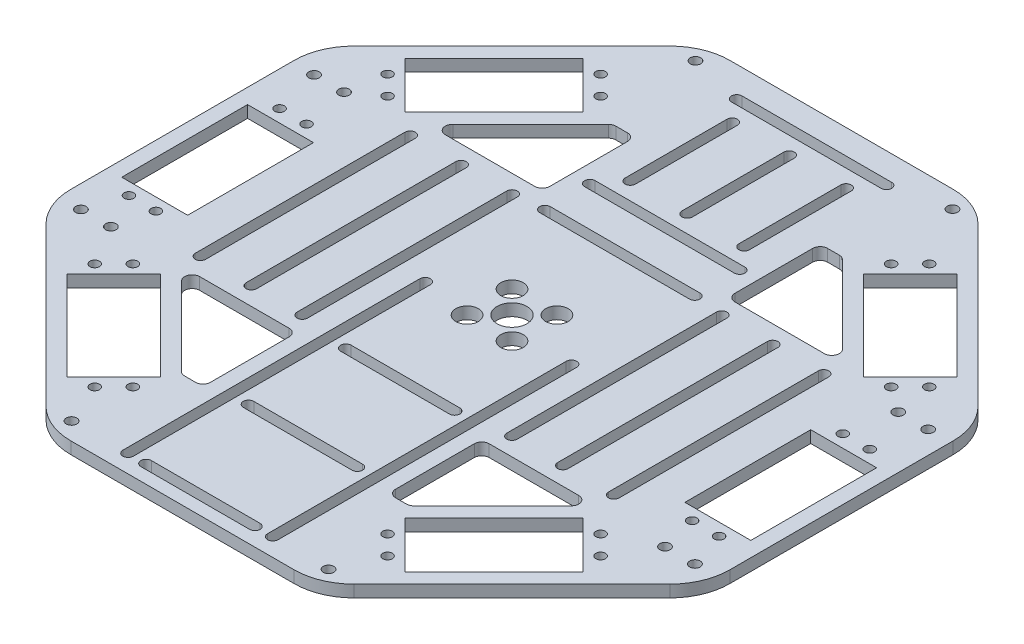
SolidWorks part; units mm, degrees
ref_plane "Front Plane" through (0, 0, 0) normal (0, 0, 1) x (1, 0, 0)
ref_plane "Top Plane" through (0, 0, 0) normal (0, 1, 0) x (1, 0, 0)
ref_plane "Right Plane" through (0, 0, 0) normal (1, 0, 0) x (0, 0, -1)
sketch "Sketch1" plane through (0, 0, 0) normal (0, 1, 0) x (1, 0, 0)
  line L1 (-110, -45.5635) -> (-45.5635, -110)
  line L2 (-45.5635, -110) -> (45.5635, -110)
  line L3 (45.5635, -110) -> (110, -45.5635)
  line L4 (110, -45.5635) -> (110, 45.5635)
  line L5 (110, 45.5635) -> (45.5635, 110)
  line L6 (45.5635, 110) -> (-45.5635, 110)
  line L7 (-45.5635, 110) -> (-110, 45.5635)
  line L8 (-110, 45.5635) -> (-110, -45.5635)
  line L12 (77.7817, -77.7817) -> (0, 0) construction
  line L21 (-20.4, -34.5422) -> (-34.5422, -20.4)
  line L22 (-20.4, -34.5422) -> (-50.0985, -64.2407)
  line L23 (-50.0985, -64.2407) -> (-64.2407, -50.0985)
  line L24 (-34.5422, -20.4) -> (-64.2407, -50.0985)
  line L25 (-38.85, -10) -> (-38.85, 10)
  line L26 (-38.85, -10) -> (-80.85, -10)
  line L27 (-80.85, -10) -> (-80.85, 10)
  line L28 (-38.85, 10) -> (-80.85, 10)
  line L29 (-34.5422, 20.4) -> (-20.4, 34.5422)
  line L30 (-34.5422, 20.4) -> (-64.2407, 50.0985)
  line L31 (-64.2407, 50.0985) -> (-50.0985, 64.2407)
  line L32 (-20.4, 34.5422) -> (-50.0985, 64.2407)
  line L37 (20.4, 34.5422) -> (34.5422, 20.4)
  line L38 (20.4, 34.5422) -> (50.0985, 64.2407)
  line L39 (50.0985, 64.2407) -> (64.2407, 50.0985)
  line L40 (34.5422, 20.4) -> (64.2407, 50.0985)
  line L41 (38.85, 10) -> (38.85, -10)
  line L42 (38.85, 10) -> (80.85, 10)
  line L43 (80.85, 10) -> (80.85, -10)
  line L44 (38.85, -10) -> (80.85, -10)
  circle A0 centre (0, 0) radius 110 construction
  circle A13 centre (0, 0) radius 110 construction
  circle A14 centre (-27.7186, -21.3546) radius 2.5
  circle A15 centre (-21.3546, -27.7186) radius 2.5
  circle A16 centre (-56.9221, -63.2861) radius 2.5
  circle A17 centre (-63.2861, -56.9221) radius 2.5
  circle A18 centre (0, 0) radius 110 construction
  circle A19 centre (-34.7, 4.5) radius 2.5
  circle A20 centre (-34.7, -4.5) radius 2.5
  circle A21 centre (-85, -4.5) radius 2.5
  circle A22 centre (-85, 4.5) radius 2.5
  circle A23 centre (0, 0) radius 110 construction
  circle A24 centre (-21.3546, 27.7186) radius 2.5
  circle A25 centre (-27.7186, 21.3546) radius 2.5
  circle A26 centre (-63.2861, 56.9221) radius 2.5
  circle A27 centre (-56.9221, 63.2861) radius 2.5
  circle A28 centre (0, 0) radius 110 construction
  circle A33 centre (0, 0) radius 110 construction
  circle A34 centre (27.7186, 21.3546) radius 2.5
  circle A35 centre (21.3546, 27.7186) radius 2.5
  circle A36 centre (56.9221, 63.2861) radius 2.5
  circle A37 centre (63.2861, 56.9221) radius 2.5
  circle A38 centre (0, 0) radius 110 construction
  circle A39 centre (34.7, -4.5) radius 2.5
  circle A40 centre (34.7, 4.5) radius 2.5
  circle A41 centre (85, 4.5) radius 2.5
  circle A42 centre (85, -4.5) radius 2.5
  circle A43 centre (0, 0) radius 110 construction
  point P15 (77.7817, -77.7817)
  point P16 (74.2462, -74.2462)
  point P17 (71.3117, -71.3117)
  point P121 (0, 0)
  dimension "D1" = 110
  dimension "D12" = 8
extrude "Baseplate" add sketch "Sketch1" along normal blind 4 contours L7 L8 L1 L2 L3 L4 L5 L6 A42 A41 A40 A39 A37 A36 A35 A34 A27 A26 A25 A24 A22 A21 A20 A19 A17 A16 A15 A14 L44 L41 | L29 L32 L31 L30 | L37 L40 L39 L38 | L41 L44 L43 L42 | L25 L28 L27 L26 | A27 | A26 | A25 | A24 | A22 | A21 | A19 | A20 | A14 | A15 | A17 | A16 | A40 | A41 | A42 | A35 | A34 | A39 | A37 | A36 | L21 L24 L23 L22 region at (1.0949, 0, 1.0949) region at (-59.85, 0, 0) region at (-42.3203, 0, -42.3203) region at (42.3203, 0, -42.3203) region at (59.85, 0, 0) region at (-27.7186, 0, 21.3546) region at (-21.3546, 0, 27.7186) region at (-56.9221, 0, 63.2861) region at (-63.2861, 0, 56.9221) region at (-34.7, 0, -4.5) region at (-34.7, 0, 4.5) region at (-85, 0, 4.5) region at (-85, 0, -4.5) region at (-21.3546, 0, -27.7186) region at (-27.7186, 0, -21.3546) region at (-63.2861, 0, -56.9221) region at (-56.9221, 0, -63.2861) region at (34.7, 0, -4.5) region at (85, 0, -4.5) region at (85, 0, 4.5)
fillet "Fillet1" radius 20 8 edges at (-110, 2, -45.5635) (-45.5635, 2, -110) (45.5635, 2, -110) (110, 2, -45.5635) (110, 2, 45.5635) (45.5635, 2, 110) (-45.5635, 2, 110) (-110, 2, 45.5635)
sketch "Sketch2" plane through (0, 4, 0) normal (0, 1, 0) x (1, 0, 0)
  line L0 (110, -37.2792) -> (110, 37.2792) construction
  line L1 (83, 16.7208) -> (105, 16.7208)
  line L2 (83, 16.7208) -> (83, -25.2792)
  line L3 (83, -25.2792) -> (105, -25.2792)
  line L4 (105, 16.7208) -> (105, -25.2792)
  circle A0 centre (98.5, 20.9208) radius 1.6
  circle A1 centre (89.5, 20.9208) radius 1.6
  circle A2 centre (89.5, -29.3792) radius 1.6
  circle A3 centre (98.5, -29.3792) radius 1.6
  point P8 (94, 16.7208)
  dimension "D1" = 3.2
  dimension "D2" = 9
  dimension "D3" = 50.3
  dimension "D4" = 22
  dimension "D5" = 42
  dimension "D6" = 4.2
  dimension "D7" = 4.5
  dimension "D8" = 5
  dimension "D9" = 12
extrude "Servo hole" cut sketch "Sketch2" against normal through all contours A0 | L4 L1 L2 L3 | A2 | A3 | A1 region at (94, 4, 4.2792) region at (98.5, 4, -20.9208) region at (89.5, 4, 29.3792) region at (98.5, 4, 29.3792)
sketch "Sketch3" plane through (0, 4, 0) normal (0, 1, 0) x (1, 0, 0)
  circle A0 centre (0, 0) radius 5
  dimension "D1" = 10
extrude "Center hole" cut sketch "Sketch3" against normal through all
pattern_circular "Servo hole pattern" count 8 over 360 about axis through (0, 4, 0) along (0, 1, 0) skipping 2, 3, 4, 5, 6 of "Servo hole"
ref_plane "Midplane" through (0, 0, 0) normal (1, 0, 0) x (0, 0, -1)
mirror "Mirror1" about plane through (0, 0, 0) normal (1, 0, 0) of "Servo hole pattern", "Servo hole"
sketch "Sketch5" plane through (0, 4, 0) normal (0, 1, 0) x (1, 0, 0)
  line L0 (-25, 36) -> (25, 36) construction
  line L1 (-25, 37.75) -> (25, 37.75)
  line L2 (-25, 34.25) -> (25, 34.25)
  line L3 (-25, 51) -> (25, 51) construction
  line L4 (-25, 52.75) -> (25, 52.75)
  line L5 (-25, 49.25) -> (25, 49.25)
  line L6 (-52, 35) -> (-52, -35) construction
  line L7 (-50.25, 35) -> (-50.25, -35)
  line L8 (-53.75, 35) -> (-53.75, -35)
  line L9 (-35, 35) -> (-35, -35) construction
  line L10 (-33.25, 35) -> (-33.25, -35)
  line L11 (-36.75, 35) -> (-36.75, -35)
  line L12 (35, 35) -> (35, -35) construction
  line L13 (36.75, 35) -> (36.75, -35)
  line L14 (33.25, 35) -> (33.25, -35)
  line L15 (52, 35) -> (52, -35) construction
  line L16 (53.75, 35) -> (53.75, -35)
  line L17 (50.25, 35) -> (50.25, -35)
  line L18 (-25, 100) -> (25, 100) construction
  line L19 (-25, 101.75) -> (25, 101.75)
  line L20 (-25, 98.25) -> (25, 98.25)
  line L21 (-19, 92.5) -> (-19, 58.5) construction
  line L22 (-17.25, 92.5) -> (-17.25, 58.5)
  line L23 (-20.75, 92.5) -> (-20.75, 58.5)
  line L24 (19, 92.5) -> (19, 58.5) construction
  line L25 (20.75, 92.5) -> (20.75, 58.5)
  line L26 (17.25, 92.5) -> (17.25, 58.5)
  line L27 (37.2792, 110) -> (-37.2792, 110) construction
  line L28 (0, 92.5) -> (0, 58.5) construction
  line L29 (1.75, 92.5) -> (1.75, 58.5)
  line L30 (-1.75, 92.5) -> (-1.75, 58.5)
  line L31 (-69, 35) -> (-69, -35) construction
  line L32 (-67.25, 35) -> (-67.25, -35)
  line L33 (-70.75, 35) -> (-70.75, -35)
  line L34 (69, 35) -> (69, -35) construction
  line L35 (70.75, 35) -> (70.75, -35)
  line L36 (67.25, 35) -> (67.25, -35)
  arc A0 (-25, 37.75) -> (-25, 34.25) centre (-25, 36) ccw
  arc A1 (25, 34.25) -> (25, 37.75) centre (25, 36) ccw
  arc A2 (-25, 52.75) -> (-25, 49.25) centre (-25, 51) ccw
  arc A3 (25, 49.25) -> (25, 52.75) centre (25, 51) ccw
  arc A4 (-50.25, 35) -> (-53.75, 35) centre (-52, 35) ccw
  arc A5 (-53.75, -35) -> (-50.25, -35) centre (-52, -35) ccw
  arc A6 (-33.25, 35) -> (-36.75, 35) centre (-35, 35) ccw
  arc A7 (-36.75, -35) -> (-33.25, -35) centre (-35, -35) ccw
  arc A8 (36.75, 35) -> (33.25, 35) centre (35, 35) ccw
  arc A9 (33.25, -35) -> (36.75, -35) centre (35, -35) ccw
  arc A10 (53.75, 35) -> (50.25, 35) centre (52, 35) ccw
  arc A11 (50.25, -35) -> (53.75, -35) centre (52, -35) ccw
  arc A12 (-25, 101.75) -> (-25, 98.25) centre (-25, 100) ccw
  arc A13 (25, 98.25) -> (25, 101.75) centre (25, 100) ccw
  arc A14 (-17.25, 92.5) -> (-20.75, 92.5) centre (-19, 92.5) ccw
  arc A15 (-20.75, 58.5) -> (-17.25, 58.5) centre (-19, 58.5) ccw
  arc A16 (20.75, 92.5) -> (17.25, 92.5) centre (19, 92.5) ccw
  arc A17 (17.25, 58.5) -> (20.75, 58.5) centre (19, 58.5) ccw
  arc A18 (1.75, 92.5) -> (-1.75, 92.5) centre (0, 92.5) ccw
  arc A19 (-1.75, 58.5) -> (1.75, 58.5) centre (0, 58.5) ccw
  arc A20 (-67.25, 35) -> (-70.75, 35) centre (-69, 35) ccw
  arc A21 (-70.75, -35) -> (-67.25, -35) centre (-69, -35) ccw
  arc A22 (70.75, 35) -> (67.25, 35) centre (69, 35) ccw
  arc A23 (67.25, -35) -> (70.75, -35) centre (69, -35) ccw
  point P2 (0, 36)
  point P7 (0, 51)
  point P14 (-52, 0)
  point P21 (-35, 0)
  point P28 (35, 0)
  point P35 (52, 0)
  point P42 (0, 100)
  point P48 (-19, 75.5)
  point P57 (19, 75.5)
  point P64 (0, 75.5)
  point P73 (-69, 0)
  point P80 (69, 0)
  dimension "D1" = 1.75
  dimension "D7" = 70
  dimension "D2" = 17
  dimension "D3" = 17
  dimension "D4" = 15
  dimension "D5" = 10
  dimension "D6" = 50
  dimension "D8" = 35
  dimension "D9" = 35
  dimension "D10" = 36
  dimension "D11" = 19
  dimension "D12" = 19
  dimension "D13" = 7.5
  dimension "D14" = 7.5
  dimension "D15" = 17
  dimension "D16" = 17
extrude "Slits" cut sketch "Sketch5" against normal through all contours L30 A19 L29 A18 | L26 A17 L25 A16 | L5 A3 L4 A2 | L2 A1 L1 A0 | L8 A5 L7 A4 | L11 A7 L10 A6 | L14 A9 L13 A8 | L17 A11 L16 A10 | L33 A21 L32 A20 | L19 A13 L20 A12 | L22 A15 L23 A14 | L35 A23 L36 A22 region at (0, 4, -36) region at (0, 4, -51) region at (-52, 4, 0) region at (-35, 4, 0) region at (35, 4, 0) region at (52, 4, 0) region at (19, 4, -75.5) region at (0, 4, -75.5) region at (-69, 4, 0)
ref_plane "Plane1" through (0, 0, 0) normal (0, 0, 1) x (1, 0, 0)
sketch "Sketch6" plane through (0, 4, 0) normal (0, 1, 0) x (1, 0, 0)
  line L0 (24.15, -4.3119) -> (24.15, -104) construction
  line L1 (25.9, -4.3119) -> (25.9, -104)
  line L2 (22.4, -4.3119) -> (22.4, -104)
  line L3 (-24.15, -104) -> (-24.15, -4.8551) construction
  line L4 (-25.9, -104) -> (-25.9, -4.8551)
  line L5 (-22.4, -104) -> (-22.4, -4.8551)
  line L6 (-37.2792, -110) -> (37.2792, -110) construction
  line L7 (-18.15, -37.3) -> (18.15, -37.3) construction
  line L8 (-18.15, -35.55) -> (18.15, -35.55)
  line L9 (-18.15, -39.05) -> (18.15, -39.05)
  line L10 (-18.15, -104) -> (18.15, -104) construction
  line L11 (-18.15, -102.25) -> (18.15, -102.25)
  line L12 (-18.15, -105.75) -> (18.15, -105.75)
  line L13 (-18.15, -69.7877) -> (18.15, -69.7877) construction
  line L14 (-18.15, -68.0377) -> (18.15, -68.0377)
  line L15 (-18.15, -71.5377) -> (18.15, -71.5377)
  arc A0 (25.9, -4.3119) -> (22.4, -4.3119) centre (24.15, -4.3119) ccw
  arc A1 (22.4, -104) -> (25.9, -104) centre (24.15, -104) ccw
  arc A2 (-25.9, -104) -> (-22.4, -104) centre (-24.15, -104) ccw
  arc A3 (-22.4, -4.8551) -> (-25.9, -4.8551) centre (-24.15, -4.8551) ccw
  arc A4 (-18.15, -35.55) -> (-18.15, -39.05) centre (-18.15, -37.3) ccw
  arc A5 (18.15, -39.05) -> (18.15, -35.55) centre (18.15, -37.3) ccw
  arc A6 (-18.15, -102.25) -> (-18.15, -105.75) centre (-18.15, -104) ccw
  arc A7 (18.15, -105.75) -> (18.15, -102.25) centre (18.15, -104) ccw
  arc A8 (-18.15, -68.0377) -> (-18.15, -71.5377) centre (-18.15, -69.7877) ccw
  arc A9 (18.15, -71.5377) -> (18.15, -68.0377) centre (18.15, -69.7877) ccw
  point P2 (24.15, -54.1559)
  point P9 (-24.15, -54.4275)
  point P15 (0, -110)
  point P19 (0, -37.3)
  point P24 (0, -104)
  point P31 (0, -69.7877)
  point P38 (0, -20.6578)
  point P39 (0, -69.6734)
  point P40 (-18.15, -69.7877)
  dimension "D2" = 1.75
  dimension "D3" = 1.75
  dimension "D7" = 1.75
  dimension "D1" = 1.75
  dimension "D10" = 1.75
  dimension "D4" = 48.3
  dimension "D5" = 24.15
  dimension "D6" = 66.7
  dimension "D8" = 6
  dimension "D9" = 6
  dimension "D11" = 6
extrude "Cut-Extrude1" cut sketch "Sketch6" against normal through all contours L9 A5 L8 A4 | L2 A1 L1 A0 | L15 A9 L14 A8 | L12 A7 L11 A6 | L5 A3 L4 A2 region at (24.15, 4, 54.1559) region at (0, 4, 37.3) region at (0, 4, 104) region at (0, 4, 69.7877)
sketch "Sketch7" plane through (0, 4, 0) normal (0, 1, 0) x (1, 0, 0)
  line L0 (-110, 37.2792) -> (-110, -37.2792) construction
  line L1 (-25.9, -104) -> (-25.9, -4.8551) construction
  circle A0 centre (-102.5, 36.4214) radius 1.75
  circle A1 centre (-92.5, 36.4214) radius 1.75
  circle A2 centre (-92.5, -41.4214) radius 1.75
  circle A3 centre (-102.5, -41.4214) radius 1.75
  circle A4 centre (-42.9, -104.1421) radius 1.75
  circle A5 centre (-42.9, 104.1421) radius 1.75
  point P12 (0, 0)
  point P13 (0, 0)
  point P14 (0, 0)
  point P15 (-91.0861, -38.0264)
  point P20 (-92.2239, -41.4214)
  point P21 (-92.3848, 41.4214)
  point P22 (-92.5, -41.4214)
  point P23 (-94.4426, 35.4987)
  point P27 (0, 0)
  point P28 (0, 0)
  point P30 (0, 0)
  dimension "D1" = 3.5
  dimension "D2" = 7.5
  dimension "D3" = 15
  dimension "D4" = 10
  dimension "D5" = 10
  dimension "D6" = 17
extrude "Cut-Extrude2" cut sketch "Sketch7" against normal blind 10 contours A0 | A1 | A3 | A2 | A4 | A5 region at (-102.5, 4, -36.4214) region at (-92.5, 4, -36.4214) region at (-92.5, 4, 41.4214) region at (-102.5, 4, 41.4214) region at (-42.9, 4, 104.1421)
ref_plane "Plane2" through (0, 0, 0) normal (-1, 0, 0) x (0, 0, 1)
mirror "Mirror2" about plane through (0, 0, 0) normal (-1, 0, 0) of "Cut-Extrude2"
sketch "Sketch8" plane through (0, 4, 0) normal (0, 1, 0) x (1, 0, 0)
  circle A0 centre (-7.5, 7.5) radius 3.75
  circle A1 centre (7.5, 7.5) radius 3.75
  circle A2 centre (-7.5, -7.5) radius 3.75
  circle A3 centre (7.5, -7.5) radius 3.75
  point P8 (0, 0)
  point P10 (0, 0)
  point P11 (0, 0)
  point P12 (0, 0)
  point P13 (0, 0)
  point P14 (-11.0211, 7.5)
  dimension "D1" = 7.5
  dimension "D2" = 7.5
  dimension "D3" = 7.5
  dimension "D4" = 7.5
  dimension "D5" = 7.5
extrude "Cut-Extrude3" cut sketch "Sketch8" against normal blind 10 contours A1 | A3 | A2 | A0 region at (7.5, 4, -7.5) region at (-7.5, 4, 7.5) region at (7.5, 4, 7.5)
sketch "Sketch9" plane through (0, 4, 0) normal (0, 1, 0) x (1, 0, 0)
  line L0 (-69.3087, -41) -> (-38.0555, -72.2532)
  line L1 (-38.0555, -72.2532) -> (-30.9, -72.2532)
  line L2 (-30.9, -72.2532) -> (-30.9, -41)
  line L3 (-30.9, -41) -> (-69.3087, -41)
  line L5 (-69.3087, 41) -> (-38.3473, 71.9613)
  line L6 (-38.3473, 71.9613) -> (-30.9, 71.9613)
  line L7 (-30.9, 71.9613) -> (-30.9, 41)
  line L8 (-30.9, 41) -> (-69.3087, 41)
  line L9 (-46.8665, 70.5132) -> (-76.565, 40.8148) construction
  line L10 (-70.5132, -46.8665) -> (-40.8148, -76.565) construction
  line L11 (-25.9, -104) -> (-25.9, -4.8551) construction
  arc A0 (-50.25, 35) -> (-53.75, 35) centre (-52, 35) ccw construction
  arc A1 (-53.75, -35) -> (-50.25, -35) centre (-52, -35) ccw construction
  point P11 (-67.0036, -41.2901)
  dimension "D1" = 5
  dimension "D2" = 5
  dimension "D3" = 5
  dimension "D4" = 6
  dimension "D5" = 6
extrude "Cut-Extrude4" cut sketch "Sketch9" against normal through all
fillet "Fillet2" radius 2.5 8 edges at (-30.9, 2, 41) (-69.3087, 2, 41) (-38.0555, 2, 72.2532) (-30.9, 2, 72.2532) (-30.9, 2, -41) (-38.3473, 2, -71.9613) (-30.9, 2, -71.9613) (-69.3087, 2, -41)
mirror "Mirror3" about plane through (0, 0, 0) normal (-1, 0, 0) of "Fillet2", "Cut-Extrude4"
